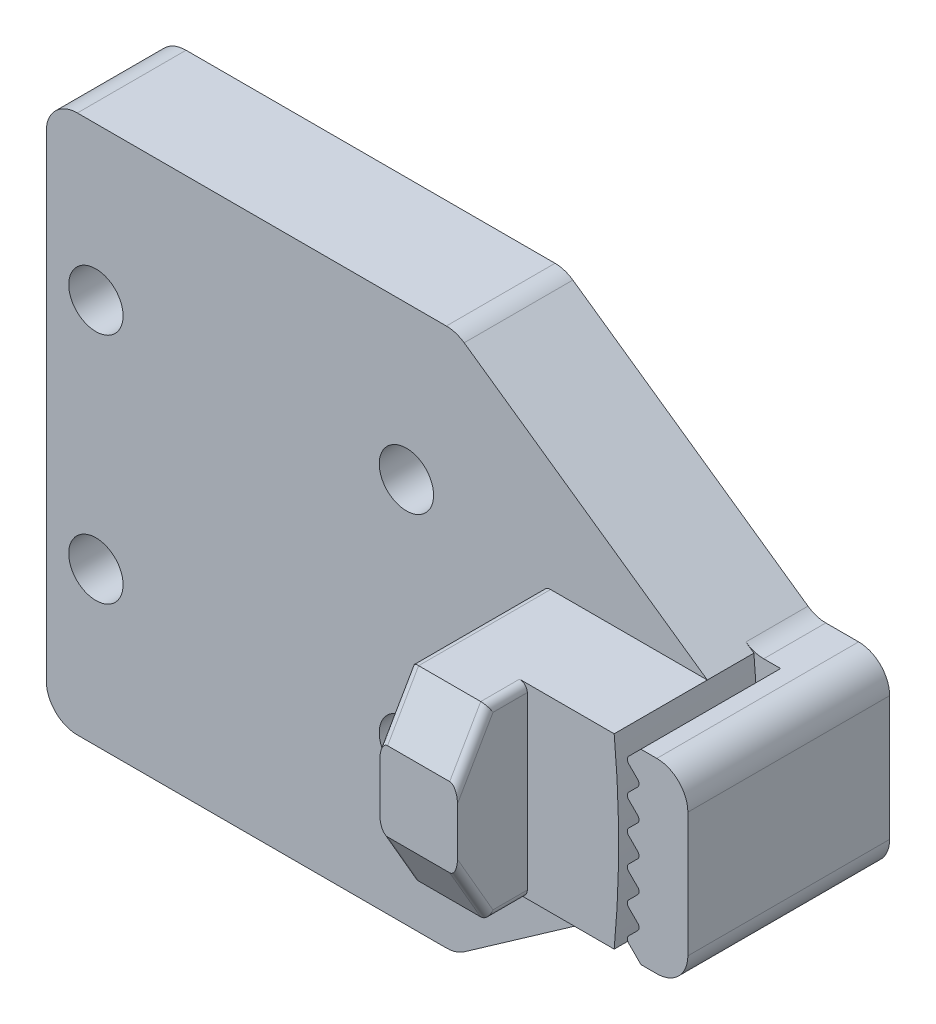
SolidWorks part; units mm, degrees
ref_plane "Спереди" through (0, 0, 0) normal (0, 0, 1) x (1, 0, 0)
ref_plane "Сверху" through (0, 0, 0) normal (0, 1, 0) x (1, 0, 0)
ref_plane "Справа" through (0, 0, 0) normal (1, 0, 0) x (0, 0, -1)
sketch "Эскиз1" plane through (0, 0, 0) normal (0, 0, 1) x (1, 0, 0)
  line L0 (-13.3352, -17.2382) -> (13.0648, -17.2382)
  line L1 (-13.3352, -17.2382) -> (-13.3352, 17.4618)
  line L2 (-13.3352, 17.4618) -> (13.0648, 17.4618)
  line L3 (13.0648, -17.2382) -> (13.0648, 17.4618)
  line L4 (13.0648, 17.4618) -> (29.2432, 6.1194)
  line L5 (29.2432, -5.8958) -> (21.8692, -5.8958)
  line L6 (13.0648, -17.2382) -> (13.0648, 17.4618)
  line L7 (29.2432, 6.1194) -> (21.8692, 6.1194)
  line L8 (30.1813, 3.3303) -> (30.757, 3.9061)
  line L9 (29.2424, 14.5413) -> (29.2424, 10.6136) construction
  line L10 (21.8692, 6.1194) -> (21.8692, -5.8958)
  line L11 (9.9589, 0.1118) -> (35.1827, 0.1118) construction
  line L12 (29.2432, -5.8958) -> (33.9894, -5.8958)
  line L13 (9.8588, 7.6118) -> (9.8588, -7.3882) construction
  line L14 (29.2432, 6.1194) -> (33.9894, 6.1194)
  line L15 (13.0648, -17.2382) -> (29.2432, -5.8958)
  line L16 (33.9894, -5.8958) -> (33.9894, 6.1194)
  line L17 (30.757, 4.3303) -> (30.1781, 4.9093)
  line L18 (29.9659, 5.1214) -> (29.9659, -8.5146) construction
  line L19 (29.2432, -5.8958) -> (29.2432, -11.5882) construction
  line L20 (30.9691, 6.1246) -> (30.1781, 5.3336)
  line L21 (29.2432, 6.6133) -> (29.2432, 6.1194) construction
  line L22 (30.1813, 2.9061) -> (30.757, 2.3303)
  line L23 (30.757, 1.9061) -> (30.1781, 1.3271)
  line L24 (30.1813, -0.6761) -> (30.757, -0.1004)
  line L25 (29.2355, 10.6136) -> (29.2424, 10.6136)
  line L26 (30.757, 0.3239) -> (30.1781, 0.9029)
  line L27 (30.1813, -1.1004) -> (30.757, -1.6761)
  line L28 (30.757, -2.1004) -> (30.1781, -2.6793)
  line L29 (30.1813, -4.6825) -> (30.757, -4.1068)
  line L30 (30.757, -3.6825) -> (30.1781, -3.1036)
  line L31 (30.1813, -5.1068) -> (30.9691, -5.8947)
  line L32 (30.9691, -5.8947) -> (30.968, -5.8958)
  circle A0 centre (-10.1412, 7.6118) radius 1.75
  circle A1 centre (9.8588, 7.6118) radius 1.75
  circle A2 centre (-10.1412, -7.3882) radius 1.75
  circle A3 centre (9.8588, -7.3882) radius 1.75
  arc A4 (29.2432, 6.1194) -> (29.2432, -5.8958) centre (-33.2517, 0.1118) cw
  arc A5 (30.1813, -4.6825) -> (30.1813, -5.1068) centre (30.3934, -4.8947) ccw
  arc A6 (30.757, -4.1068) -> (30.757, -3.6825) centre (30.5449, -3.8947) ccw
  arc A7 (30.1781, -2.6793) -> (30.1781, -3.1036) centre (30.3902, -2.8914) ccw
  arc A8 (30.757, -1.6761) -> (30.757, -2.1004) centre (30.5449, -1.8882) cw
  arc A9 (30.1813, -0.6761) -> (30.1813, -1.1004) centre (30.3934, -0.8882) ccw
  arc A10 (30.757, -0.1004) -> (30.757, 0.3239) centre (30.5449, 0.1118) ccw
  arc A11 (30.1781, 1.3271) -> (30.1781, 0.9029) centre (30.3902, 1.115) ccw
  arc A12 (30.757, 2.3303) -> (30.757, 1.9061) centre (30.5449, 2.1182) cw
  arc A13 (30.1813, 3.3303) -> (30.1813, 2.9061) centre (30.3934, 3.1182) ccw
  arc A14 (30.757, 3.9061) -> (30.757, 4.3303) centre (30.5449, 4.1182) ccw
  arc A15 (30.1781, 4.9093) -> (30.1781, 5.3336) centre (30.3902, 5.1214) cw
  point P34 (29.9691, 3.1182)
  point P40 (29.9691, -0.8882)
  point P46 (29.9691, -4.8947)
  dimension "D4" = 3.5
  dimension "D3" = 0.3
  dimension "D1" = 26.4
  dimension "D2" = 34.7
  dimension "D5" = 16.1776
extrude "Бобышка-Вытянуть1" add sketch "Эскиз1" along normal blind 4 and the other way blind 3 contours L3 L15 L10 L4 | L0 L3 L2 L1 A3 A2 A1 A0 | L10 | L30 region at (-0.1349, 0.1118, 0) region at (18.0953, 0.1118, 0) region at (25.6527, 0.1118, 0) region at (32.2197, 0.1125, 0)
extrude "Бобышка-Вытянуть2" add sketch "Эскиз1<3>" along normal blind 6 from offset 4 contours L10 | L30 region at (25.6527, 0.1118, 0) region at (32.2197, 0.1125, 0)
sketch "Эскиз1<3>" plane through (0, 0, 0) normal (0, 0, 1) x (1, 0, 0) same geometry as "Эскиз1"
extrude "Бобышка-Вытянуть3" add sketch "Эскиз1<4>" along normal blind 1 and the other way blind 3 contours L30 region at (29.9824, 0.1095, 0)
sketch "Эскиз1<4>" plane through (0, 0, 0) normal (0, 0, 1) x (1, 0, 0) same geometry as "Эскиз1"
fillet "Скругление1" radius 2 8 edges at (13.0648, 17.4618, 0.5) (13.0648, -17.2382, 0.5) (-13.3352, -17.2382, 0.5) (-13.3352, 17.4618, 0.5) (33.9894, -5.8958, 3.5) (33.9894, 6.1194, 3.5) (29.2432, -5.8958, -1) (29.2432, 6.1194, -1)
sketch "Эскиз2" plane through (0, 0, 4) normal (0, 0, 1) x (1, 0, 0)
  line L0 (29.2432, 6.1194) -> (21.8692, 6.1194) construction
  line L1 (23.647, 6.1194) -> (18.647, 6.1194)
  line L2 (23.647, 6.1194) -> (23.647, -5.8958)
  line L3 (23.647, -5.8958) -> (18.647, -5.8958)
  line L4 (18.647, 6.1194) -> (18.647, -5.8958)
  line L5 (29.2432, -5.8958) -> (21.8692, -5.8958) construction
  dimension "D1" = 5
extrude "Бобышка-Вытянуть4" add sketch "Эскиз2" along normal blind 10.5
chamfer "Фаска2" distance 2 angle 60 2 edges at (21.147, -5.8958, 14.5) (21.147, 6.1194, 14.5) first distance on face at (23.8457, -5.8958, 9.5) first distance on face at (23.8457, 6.1194, 9.5)
fillet "Скругление2" radius 0.5 8 edges at (23.647, -5.8958, 11.25) (23.647, 6.1194, 11.25) (18.647, -5.8958, 8.25) (18.647, -4.1638, 13.5) (18.647, 4.3874, 13.5) (18.647, 6.1194, 8.25) (23.647, 4.3874, 13.5) (23.647, -4.1638, 13.5)
